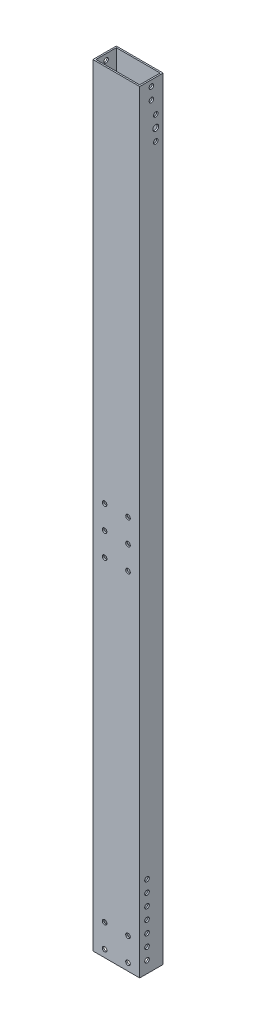
SolidWorks part; units mm, degrees
material "6061-T6 (SS)"
ref_plane "Front Plane" through (0, 0, 0) normal (0, 0, 1) x (1, 0, 0)
ref_plane "Top Plane" through (0, 0, 0) normal (0, 1, 0) x (1, 0, 0)
ref_plane "Right Plane" through (0, 0, 0) normal (1, 0, 0) x (0, 0, -1)
sketch "Sketch1" plane through (0, 0, 0) normal (0, 0, 1) x (1, 0, 0)
  line L1 (-25.4, -419.1) -> (25.4, -419.1)
  line L2 (-25.4, -419.1) -> (-25.4, 419.1)
  line L3 (-25.4, 419.1) -> (25.4, 419.1)
  line L4 (25.4, -419.1) -> (25.4, 419.1)
  line L5 (-25.4, -419.1) -> (25.4, 419.1) construction
  line L6 (-25.4, 419.1) -> (25.4, -419.1) construction
  point P0 (0, 0)
  dimension "D1" = 50.8
  dimension "D2" = 838.2
extrude "Boss-Extrude1" add sketch "Sketch1" along normal mid plane 25.4
shell "Shell1" thickness 1.5875 removed face at (0, -419.1, 0) removed face at (0, 419.1, 0)
sketch "Sketch3" plane through (0, 0, 0) normal (1, 0, 0) x (0, 0, -1)
  line L0 (-12.7, -419.1) -> (12.7, -419.1) construction
  line L1 (-12.7, 419.1) -> (12.7, 419.1) construction
  circle A0 centre (0, 400.05) radius 2.4892
  circle A1 centre (0, 412.75) radius 2.4892
  point P6 (0, -419.1)
  dimension "D1" = 4.9784
  dimension "D2" = 6.35
  dimension "D3" = 12.7
extrude "Cut-Extrude1" cut sketch "Sketch3" against normal through all both and the other way through all
sketch "Sketch4" plane through (0, 0, 0) normal (1, 0, 0) x (0, 0, -1)
  line L0 (12.7, 419.1) -> (12.7, -419.1) construction
  line L3 (-12.7, 419.1) -> (12.7, 419.1) construction
  circle A0 centre (4.7625, 371.475) radius 3.175
  circle A1 centre (4.7625, 384.175) radius 2.4892
  circle A2 centre (4.7625, 358.775) radius 2.4892
  dimension "D1" = 6.35
  dimension "D4" = 4.9784
  dimension "D2" = 7.9375
  dimension "D5" = 12.7
  dimension "D6" = 12.7
  dimension "D3" = 47.625
extrude "Cut-Extrude2" cut sketch "Sketch4" against normal through all both and the other way through all
sketch "Sketch5" plane through (0, 0, 0) normal (0, 0, 1) x (1, 0, 0)
  line L1 (-15.875, 384.9687) -> (15.875, 384.9687)
  line L2 (-15.875, 384.9687) -> (-15.875, 357.9812)
  line L3 (-15.875, 357.9812) -> (15.875, 357.9812)
  line L4 (15.875, 384.9687) -> (15.875, 357.9812)
  line L6 (25.4, 419.1) -> (-25.4, 419.1) construction
  point P4 (-15.875, 371.475)
  point P8 (0, 384.9687)
  point P9 (0, 419.1)
  dimension "D1" = 31.75
  dimension "D2" = 26.9875
  dimension "D3" = 47.625
extrude "Cut-Extrude3" cut sketch "Sketch5" against normal through all
fillet "Fillet1" radius 3.175 4 edges at (15.875, 384.9687, -11.9062) (15.875, 357.9812, -11.9062) (-15.875, 357.9812, -11.9062) (-15.875, 384.9687, -11.9062)
sketch "Sketch6" plane through (0, 0, 0) normal (0, 0, 1) x (1, 0, 0)
  line L0 (-25.4, 419.1) -> (-25.4, -419.1) construction
  line L1 (-25.4, -419.1) -> (25.4, -419.1) construction
  circle A0 centre (-12.7, 7.9375) radius 2.4892
  circle A1 centre (12.7, 7.9375) radius 2.4892
  circle A2 centre (12.7, -17.4625) radius 2.4892
  circle A3 centre (12.7, -42.8625) radius 2.4892
  circle A4 centre (-12.7, -17.4625) radius 2.4892
  circle A5 centre (-12.7, -42.8625) radius 2.4892
  circle A6 centre (-12.7, -411.1625) radius 2.4892
  circle A7 centre (12.7, -411.1625) radius 2.4892
  circle A8 centre (12.7, -385.7625) radius 2.4892
  circle A9 centre (-12.7, -385.7625) radius 2.4892
  dimension "D1" = 4.9784
  dimension "D3" = 427.0375
  dimension "D7" = 25.4
  dimension "D2" = 12.7
  dimension "D6" = 25.4
  dimension "D8" = 7.9375
  dimension "D9" = 12.7
  dimension "D12" = 25.4
  dimension "D13" = 25.4
  dimension "D4" = 2
  dimension "D5" = 3
  dimension "D10" = 2
  dimension "D11" = 2
extrude "Cut-Extrude4" cut sketch "Sketch6" along normal through all both and the other way through all
sketch "Sketch7" plane through (0, 0, 0) normal (1, 0, 0) x (0, 0, -1)
  line L0 (-12.7, -419.1) -> (12.7, -419.1) construction
  line L2 (-12.7, -419.1) -> (-12.7, 419.1) construction
  circle A0 centre (-4.7625, -406.4) radius 2.4892
  circle A1 centre (-4.7625, -393.7) radius 2.4892
  circle A2 centre (-4.7625, -381) radius 2.4892
  circle A3 centre (-4.7625, -368.3) radius 2.4892
  circle A4 centre (-4.7625, -355.6) radius 2.4892
  circle A5 centre (-4.7625, -342.9) radius 2.4892
  circle A6 centre (-4.7625, -330.2) radius 2.4892
  dimension "D1" = 4.9784
  dimension "D5" = 12.7
  dimension "D2" = 12.7
  dimension "D3" = 7.9375
  dimension "D4" = 7
extrude "Cut-Extrude5" cut sketch "Sketch7" against normal through all both and the other way through all
equation "\"D6@Sketch4\"=\"D5@Sketch4\""
